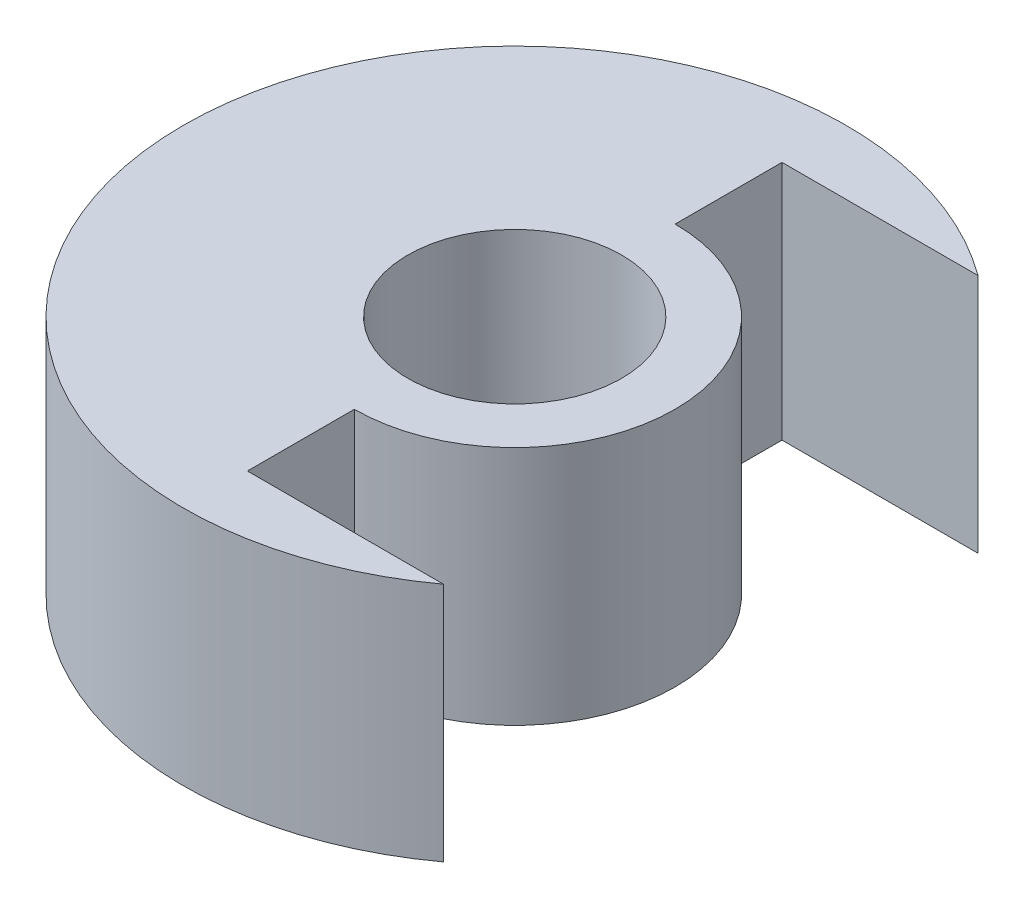
SolidWorks part; units mm, degrees
ref_plane "Alzado" through (0, 0, 0) normal (0, 0, 1) x (1, 0, 0)
ref_plane "Planta" through (0, 0, 0) normal (0, 1, 0) x (1, 0, 0)
ref_plane "Vista lateral" through (0, 0, 0) normal (1, 0, 0) x (0, 0, -1)
sketch "Croquis1" plane through (0, 0, 0) normal (0, 1, 0) x (1, 0, 0)
  circle A0 centre (0, 0) radius 62
  dimension "D1" = 124
extrude "Saliente-Extruir1" add sketch "Croquis1" along normal blind 45
sketch "Croquis3" plane through (0, 0, 0) normal (0, -1, 0) x (1, 0, 0)
  circle A0 centre (0, 0) radius 23.5
  dimension "D1" = 47
extrude "Cortar-Extruir1" cut sketch "Croquis3" against normal blind 8
sketch "Croquis4" plane through (0, 0, 0) normal (0, -1, 0) x (1, 0, 0)
  circle A0 centre (0, 0) radius 20
  circle A1 centre (0, 0) radius 23.5 construction
  dimension "D1" = 40
extrude "Cortar-Extruir2" cut sketch "Croquis4" against normal through all
sketch "Croquis5" plane through (0, 0, 0) normal (0, -1, 0) x (1, 0, 0)
  line L0 (24.75, 0) -> (-24.75, 0) construction
  line L1 (30, -3) -> (380, -3) construction
  line L2 (30, -3) -> (30, 3) construction
  line L3 (30, 3) -> (380, 3) construction
  line L4 (380, -3) -> (380, 3) construction
  line L5 (30, -3) -> (380, 3) construction
  line L6 (30, 3) -> (380, -3) construction
  line L7 (0, -24.75) -> (0, 24.75) construction
  line L8 (0, 30) -> (0, 50)
  line L9 (0, 50) -> (36.6606, 50)
  line L10 (110, 15) -> (110, -15)
  line L11 (110, 15) -> (36.6606, 50)
  line L12 (0, -50) -> (36.6606, -50)
  line L13 (0, -30) -> (0, -50)
  line L14 (36.6606, -50) -> (110, -15)
  arc A0 (0, -30) -> (0, 30) centre (0, 0) ccw
  circle A1 centre (0, 0) radius 62 construction
  point P0 (205, 0)
  point P10 (30, 0)
  point P20 (110, 0)
  dimension "D1" = 6
  dimension "D2" = 30
  dimension "D3" = 350
  dimension "D4" = 20
  dimension "D5" = 30
  dimension "D6" = 80
extrude "Cortar-Extruir3" cut sketch "Croquis5" against normal through all
sketch "Croquis9" [suppressed] plane through (0, 0, 0) normal (0, -1, 0) x (1, 0, 0)
  line L0 (24.75, 0) -> (-24.75, 0) construction
  arc A0 (-20.1503, 53.8537) -> (-20.1503, -53.8537) centre (0, 0) ccw
  arc A1 (-15.7698, 42.1463) -> (-15.7698, -42.1463) centre (0, 0) ccw
  arc A2 (-15.7698, 42.1463) -> (-20.1503, 53.8537) centre (-17.96, 48) ccw
  arc A3 (-15.7698, -42.1463) -> (-20.1503, -53.8537) centre (-17.96, -48) cw
  dimension "D1" = 115
  dimension "D2" = 90
  dimension "D3" = 48
sketch "Croquis10" plane through (0, 0, 0) normal (1, 0, 0) x (0, 0, -1)
  line L0 (0, 24.7835) -> (0, -24.7835) construction
  line L1 (-4, 0) -> (4, 0)
  line L2 (-4, 0) -> (-4, 1)
  line L3 (-4, 1) -> (4, 1)
  line L4 (4, 0) -> (4, 1)
  line L5 (-4, 0) -> (4, 1) construction
  line L6 (-4, 1) -> (4, 0) construction
  line L7 (54.2695, 0) -> (-54.2695, 0) construction
  point P0 (0, 0.5)
  dimension "D1" = 1
  dimension "D2" = 8
extrude "Cortar-Extruir7" [suppressed] cut sketch "Croquis10" along normal up to surface (3.5001 mm away) from surface
fillet "Redondeo2" [suppressed] radius 1
sketch "Croquis11" [suppressed] plane through (0, 45, 0) normal (0, 1, 0) x (1, 0, 0)
  line L0 (-24.7845, 0) -> (24.7845, 0) construction
  arc A0 (-19.1866, 51.278) -> (-19.1866, -51.278) centre (0, 0) ccw
  arc A1 (-16.7335, 44.722) -> (-16.7335, -44.722) centre (0, 0) ccw
  arc A2 (-16.7335, 44.722) -> (-19.1866, 51.278) centre (-17.96, 48) ccw
  arc A3 (-15.7698, 42.1463) -> (-20.1503, 53.8537) centre (-17.96, 48) ccw construction
  arc A4 (-16.7335, -44.722) -> (-19.1866, -51.278) centre (-17.96, -48) cw
  dimension "D1" = 3.5
